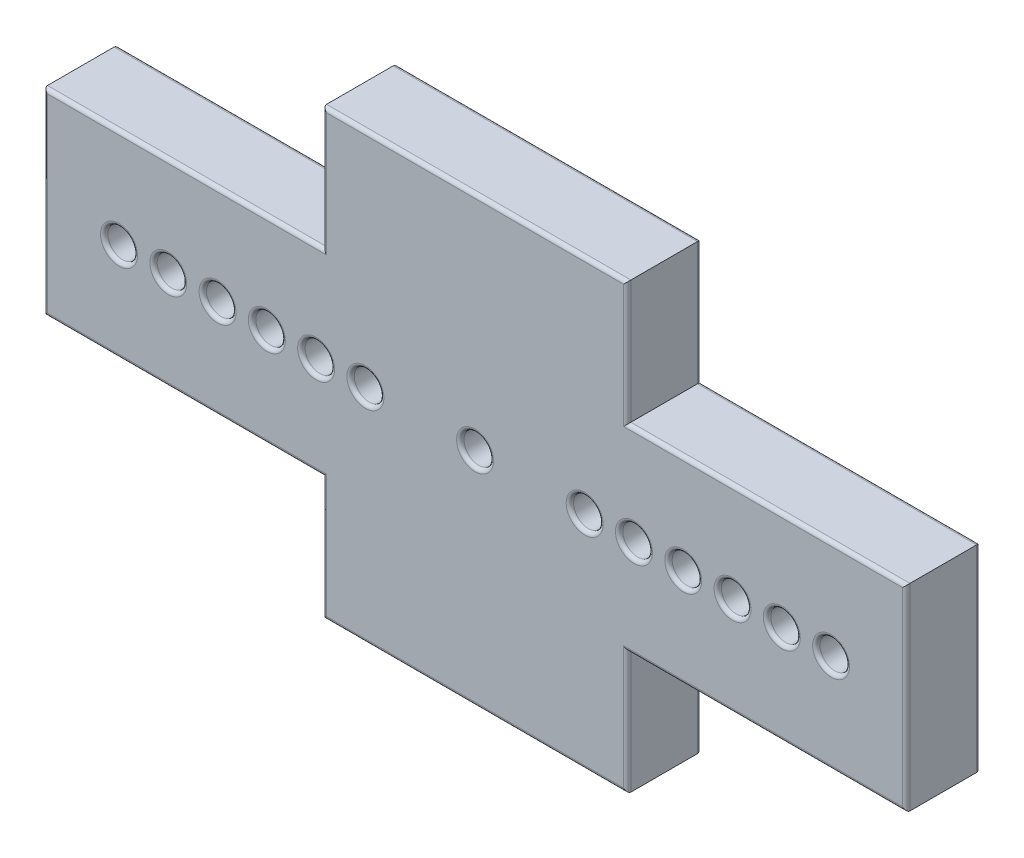
SolidWorks part; units mm, degrees
ref_plane "Płaszczyzna przednia" through (0, 0, 0) normal (0, 0, 1) x (1, 0, 0)
ref_plane "Płaszczyzna górna" through (0, 0, 0) normal (0, 1, 0) x (1, 0, 0)
ref_plane "Płaszczyzna prawa" through (0, 0, 0) normal (1, 0, 0) x (0, 0, -1)
sketch "Szkic1" plane through (0, 0, 0) normal (0, 0, 1) x (1, 0, 0)
  line L0 (-17.5, -4) -> (-17.5, 4)
  line L1 (-6.175, -9) -> (6.175, -9) construction
  line L2 (-6.175, -9) -> (-6.175, 9) construction
  line L3 (-6.175, 9) -> (6.175, 9) construction
  line L4 (6.175, -9) -> (6.175, 9) construction
  line L5 (-6.175, -9) -> (6.175, 9) construction
  line L6 (-6.175, 9) -> (6.175, -9) construction
  line L7 (-17.5, -4) -> (17.5, -4) construction
  line L8 (-17.5, -4) -> (-17.5, 4) construction
  line L9 (-17.5, 4) -> (17.5, 4) construction
  line L10 (17.5, -4) -> (17.5, 4) construction
  line L11 (-17.5, -4) -> (17.5, 4) construction
  line L12 (-17.5, 4) -> (17.5, -4) construction
  line L13 (-17.5, 4) -> (-6.175, 4)
  line L14 (-6.175, 4) -> (-6.175, 9)
  line L15 (-6.175, 9) -> (6.175, 9)
  line L16 (6.175, 9) -> (6.175, 4)
  line L17 (6.175, 4) -> (17.5, 4)
  line L18 (17.5, 4) -> (17.5, -4)
  line L19 (17.5, -4) -> (6.175, -4)
  line L20 (6.175, -4) -> (6.175, -9)
  line L21 (6.175, -9) -> (-6.175, -9)
  line L22 (-6.175, -9) -> (-6.175, -4)
  line L23 (-6.175, -4) -> (-17.5, -4)
  point P0 (0, 0)
  point P6 (0, 0)
  dimension "D1" = 8
  dimension "D2" = 35
  dimension "D3" = 18
  dimension "D4" = 12.35
extrude "Dodanie-wyciągnięcie1" add sketch "Szkic1" along normal mid plane 3
sketch "Szkic2" plane through (0, 0, 1.5) normal (0, 0, 1) x (1, 0, 0)
  line L1 (0, -9) -> (0, 9) construction
  line L2 (6.175, 9) -> (-6.175, 9) construction
  circle A0 centre (0, 0) radius 3.45 construction
  circle A13 centre (0, 0) radius 0.6
  point P22 (0, 0)
  dimension "D1" = 6.9
  dimension "D7" = 1.2
extrude "Wytnij-wyciągnięcie1" cut sketch "Szkic2" against normal through all
sketch "Szkic3" plane through (0, 0, 1.5) normal (0, 0, 1) x (1, 0, 0)
  line L0 (-4.45, 0) -> (-6.45, 0) construction
  circle A0 centre (-4.45, 0) radius 0.6
  circle A1 centre (-6.45, 0) radius 0.6
  circle A2 centre (-8.45, 0) radius 0.6
  circle A3 centre (-10.45, 0) radius 0.6
  circle A4 centre (-12.45, 0) radius 0.6
  circle A5 centre (-14.45, 0) radius 0.6
  dimension "D1" = 1.2
  dimension "D2" = 4.45
  dimension "D4" = 2
  dimension "D3" = 6
extrude "Wytnij-wyciągnięcie2" cut sketch "Szkic3" against normal through all
mirror "Lustro1" about plane through (0, 0, 0) normal (1, 0, 0) of "Wytnij-wyciągnięcie2"
fillet "Zaokrąglenie1" radius 0.15 50 edges at (0, 9, -1.5) (-6.175, 6.5, -1.5) (-11.8375, 4, -1.5) (-17.5, 0, -1.5) (-11.8375, -4, -1.5) (-6.175, -6.5, -1.5) (0, -9, -1.5) (6.175, -6.5, -1.5) (11.8375, -4, -1.5) (17.5, 0, -1.5) (11.8375, 4, -1.5) (6.175, 6.5, -1.5) (0.6, 0, -1.5) (-13.85, 0, -1.5) (-11.85, 0, -1.5) (-9.85, 0, -1.5) (-7.85, 0, -1.5) (-5.85, 0, -1.5) (-3.85, 0, -1.5) (13.85, 0, -1.5) (11.85, 0, -1.5) (9.85, 0, -1.5) (7.85, 0, -1.5) (5.85, 0, -1.5) (3.85, 0, -1.5) (11.8375, 4, 1.5) (17.5, 0, 1.5) (11.8375, -4, 1.5) (6.175, -6.5, 1.5) (0, -9, 1.5) (-6.175, -6.5, 1.5) (-11.8375, -4, 1.5) (-17.5, 0, 1.5) (-11.8375, 4, 1.5) (-6.175, 6.5, 1.5) (0, 9, 1.5) (6.175, 6.5, 1.5) (0.6, 0, 1.5) (-13.85, 0, 1.5) (-11.85, 0, 1.5) (-9.85, 0, 1.5) (-7.85, 0, 1.5) (-5.85, 0, 1.5) (-3.85, 0, 1.5) (13.85, 0, 1.5) (11.85, 0, 1.5) (9.85, 0, 1.5) (7.85, 0, 1.5) (5.85, 0, 1.5) (3.85, 0, 1.5)
